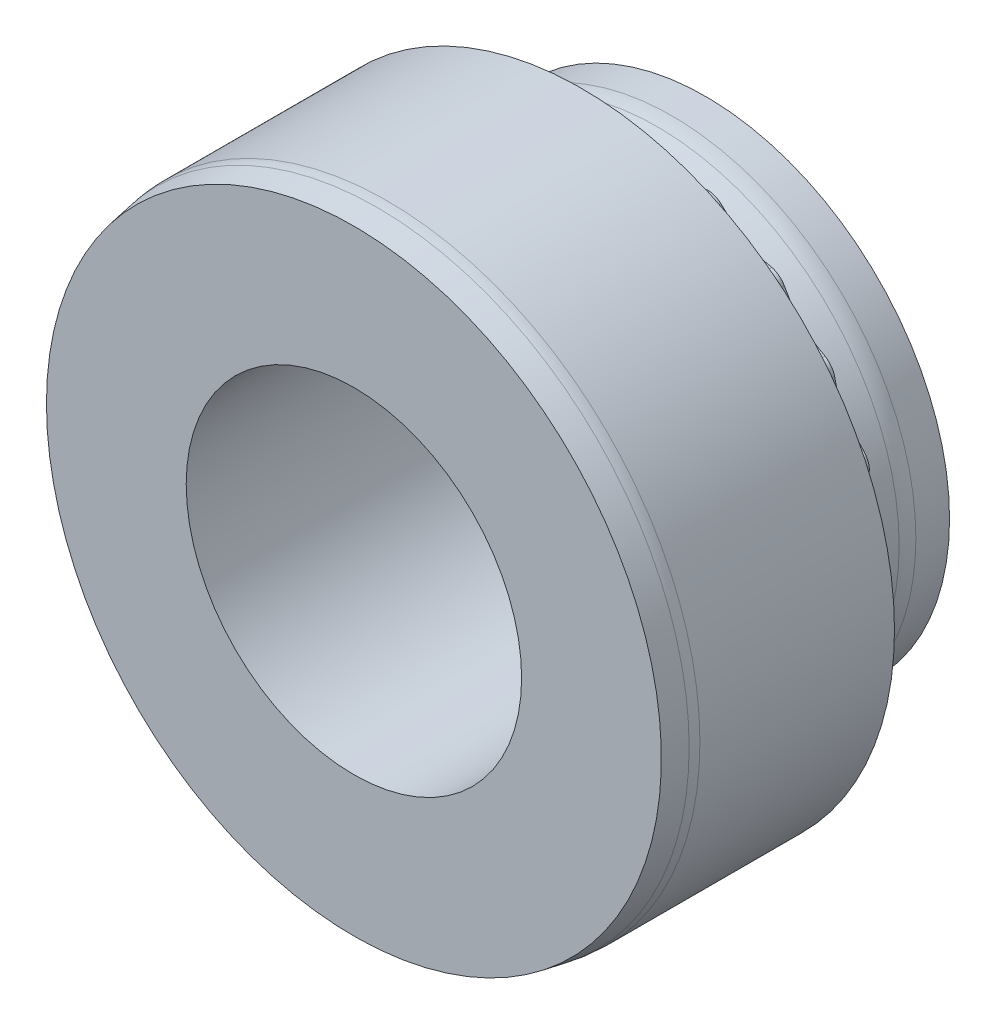
SolidWorks part; units mm, degrees
material "Alloy Steel"
ref_plane "Front Plane" through (0, 0, 0) normal (0, 0, 1) x (1, 0, 0)
ref_plane "Top Plane" through (0, 0, 0) normal (0, 1, 0) x (1, 0, 0)
ref_plane "Right Plane" through (0, 0, 0) normal (1, 0, 0) x (0, 0, -1)
sketch "Sketch1" plane through (0, 0, 0) normal (1, 0, 0) x (0, 0, -1)
  line L0 (0, -4.365) -> (0, 4.365) construction
  line L1 (0, 4.365) -> (-0.7367, 4.365) construction
  line L2 (-1.6207, 4.1281) -> (-1.6207, 5.1707) construction
  line L3 (-1.6207, 5.1707) -> (-2.21, 5.1707) construction
  line L4 (-2.21, 5.1707) -> (-2.21, 5.59) construction
  line L5 (-2.21, 5.59) -> (-6.29, 5.59) construction
  line L9 (-6.29, 0) -> (0, 0) construction
  line L10 (-6.29, -5.59) -> (-6.29, 5.59) construction
  line L11 (-0.7367, 4.365) -> (-1.6207, 4.1281) construction
  line L12 (-3.145, -3) -> (-3.145, 3) construction
  point P4 (0, 0)
  point P17 (-6.29, 0)
  point P19 (-6.29, 5.59)
  point P20 (-6.29, 0)
  point P24 (-3.145, 0)
  point P26 (-6.29, 0)
  dimension "C" = 8.73
  dimension "A" = 2.21
  dimension "Head OD" = 11.18
  dimension "D9" = 5.1707
  dimension "D10" = 0.7367
  dimension "D11" = 75
  dimension "Thread Size" = 6
  dimension "Head Height" = 4.08
  dimension "D2" = 0.5893
sketch "Sketch2" plane through (0, 0, 0) normal (1, 0, 0) x (0, 0, -1)
  line L0 (0, 0) -> (0, 4.365)
  line L1 (0, -4.365) -> (0, 4.365) construction
  line L2 (0, 4.365) -> (-0.7367, 4.365)
  line L3 (-0.7367, 4.365) -> (-1.6207, 4.1281)
  line L4 (-1.6207, 4.1281) -> (-1.6207, 5.1707)
  line L5 (-1.6207, 5.1707) -> (-2.21, 5.1707)
  line L6 (-2.21, 5.1707) -> (-2.21, 5.59)
  line L7 (-2.21, 5.59) -> (-6.29, 5.59)
  line L10 (-6.29, 0) -> (0, 0)
  line L12 (-6.29, 5.59) -> (-6.29, 0)
revolve "Revolve1" add sketch "Sketch2" angle 360 about L9
sketch "Sketch5" plane through (0, 0, 1.6207) normal (0, 0, -1) x (-1, 0, 0)
  line L0 (0, 0) -> (-5.1707, 0) construction
  line L1 (-5.1191, -0.7289) -> (-4.6537, 0)
  line L2 (-4.6537, 0) -> (-5.1191, 0.7289)
  circle A0 centre (0, 0) radius 5.1707 construction
  arc A1 (-5.1191, 0.7289) -> (-5.1191, -0.7289) centre (0, 0) ccw
  point P6 (-5.1707, 0)
  dimension "D2" = 4.6537
  dimension "D1" = 1.4627
extrude "Cut-Extrude2" cut sketch "Sketch5" against normal up to surface (0.5893 mm away) up to face at (5.59, 0, 2.21)
fillet "Fillet3" radius 0.2194 1 edges at (4.6537, 0, 1.9153)
pattern_circular "CirPattern1" count 24 over 360 about axis through (0, 0, 6.29) along (0, 0, 1) of "Cut-Extrude2", "Fillet3"
fillet "Fillet4" radius 0.2194 24 edges at (4.0656, 3.1197, 1.9153) (3.1197, 4.0656, 1.9153) (1.9611, 4.7345, 1.9153) (0.6689, 5.0808, 1.9153) (-1.9611, 4.7345, 1.9153) (-0.6689, 5.0808, 1.9153) (-3.1197, 4.0656, 1.9153) (-4.0656, 3.1197, 1.9153) (-4.7345, 1.9611, 1.9153) (-5.0808, 0.6689, 1.9153) (-4.7345, -1.9611, 1.9153) (-5.0808, -0.6689, 1.9153) (-4.0656, -3.1197, 1.9153) (-3.1197, -4.0656, 1.9153) (-1.9611, -4.7345, 1.9153) (-0.6689, -5.0808, 1.9153) (0.6689, -5.0808, 1.9153) (1.9611, -4.7345, 1.9153) (3.1197, -4.0656, 1.9153) (4.0656, -3.1197, 1.9153) (4.7345, -1.9611, 1.9153) (5.0808, -0.6689, 1.9153) (4.7345, 1.9611, 1.9153) (5.0808, 0.6689, 1.9153)
sketch "Sketch11" plane through (0, 0, 0) normal (0, 1, 0) x (1, 0, 0)
  line L0 (4.6537, -1.6207) -> (5.1707, -1.8089)
  line L2 (5.1707, -1.8089) -> (5.1707, -1.6207)
  line L3 (0, -1.6207) -> (5.1707, -1.6207) construction
  line L4 (4.6537, -1.6207) -> (5.1707, -1.6207)
  line L5 (0, -6.29) -> (0, 0) construction
  dimension "D2" = 4.6537
  dimension "D1" = 20
revolve "Cut-Revolve3" cut sketch "Sketch11" angle 360 about L9
sketch "Sketch12" plane through (0, 0, 0) normal (1, 0, 0) x (0, 0, -1)
  line L0 (-6.29, 0) -> (0, 0)
  line L1 (0, 0) -> (0, -3)
  line L2 (0, -4.365) -> (0, 4.365) construction
  line L3 (0, -3) -> (-6.29, -3)
  line L5 (-6.29, -3) -> (-6.29, 0)
revolve "Cut-Revolve4" cut sketch "Sketch12" angle 360 about L9
chamfer "Chamfer1" distance 0.51 angle 10 1 edges at (5.59, 0, 6.29) first distance on face at (5.59, 0, 6.29)
fillet "Fillet5" radius 1.02 2 edges at (-5.59, 0, 5.78) (4.365, 0, 0.7367)
sketch "Sketch17" plane through (0, 0, 6.29) normal (0, 0, 1) x (1, 0, 0)
  line L0 (0, 3) -> (0, -3) construction
  line L1 (0, 0) -> (-2.1213, -2.1213) construction
  circle A0 centre (0, 0) radius 3 construction
  point P8 (-2.1213, -2.1213)
  dimension "D1" = 45
sketch "Sketch13" [suppressed] plane through (0, 0, 0) normal (0, 0, -1) x (-1, 0, 0)
  circle A0 centre (0, 0) radius 3 construction
  circle A1 centre (0, 0) radius 3
curve "Helix/Spiral1" [suppressed] pitch 0.7937 height 7.0838 turns 8.9244 parameters "Thread Pitch"=0.7937
sketch "Sketch14" [suppressed] plane through (0, 0, 0) normal (1, 0, 0) x (0, 0, -1)
  line L0 (-0.0496, 3.0859) -> (0.7441, 3.0859) construction
  line L1 (-0.0496, 3.0859) -> (0.3473, 2.3985) construction
  line L2 (0.3473, 2.3985) -> (0.7441, 3.0859) construction
  line L3 (0.3473, 3.0859) -> (0.3473, 3) construction
  line L4 (0.3473, 2.3985) -> (0.3473, 2.4844) construction
  line L5 (0.2977, 2.4844) -> (0.3969, 2.4844) construction
  line L6 (0, 3) -> (0.6945, 3) construction
  line L7 (-0.0248, 3.043) -> (0.7193, 3.043) construction
  line L8 (-0.0248, 3.043) -> (0.7193, 3.043)
  line L9 (0.7193, 3.043) -> (0.3969, 2.4844)
  line L10 (0.3969, 2.4844) -> (0.2977, 2.4844)
  line L11 (0.2977, 2.4844) -> (-0.0248, 3.043)
  point P12 (0.3473, 3.043)
  dimension "D1" = 0.7937
  dimension "D2" = 0.0992
sweep "Sweep1" [suppressed] add profiles "Sketch14" path "Helix/Spiral1"
sketch "Sketch15" [suppressed] plane through (0, 0, 0) normal (0, 0, -1) x (-1, 0, 0)
  circle A2 centre (0, 0) radius 3.1191
  circle A3 centre (0, 0) radius 3.1191
  dimension "D1" = 0.1191
extrude "Cut-Extrude3" [suppressed] cut sketch "Sketch15" against normal through all draft 47 and the other way through all draft 47
sketch "Sketch16" [suppressed] plane through (0, 0, 6.29) normal (0, 0, 1) x (1, 0, 0)
  circle A1 centre (0, 0) radius 3.1191
  circle A2 centre (0, 0) radius 3.1191
  dimension "D1" = 0
extrude "Cut-Extrude4" [suppressed] cut sketch "Sketch16" against normal through all draft 47 and the other way through all draft 47
equation "\"D9@Sketch1\"=\"Head OD@Sketch1\" / 2 * .925"
equation "\"D10@Sketch1\"=\"A@Sketch1\" / 3"
equation "\"D1@Sketch5\" =  ( \"Head OD@Sketch1\" * 3.14 )  / 24"
equation "\"D2@Sketch5\"=\"D9@Sketch1\"*.9"
equation "\"D1@Fillet3\"=\"D1@Sketch5\"*.15"
equation "\"D1@Fillet4\"=\"D1@Fillet3\""
equation "\"D2@Sketch1\"=\"A@Sketch1\"/3.75"
equation "\"D1@Chamfer1\"=\"Head Height@Sketch1\"/8"
equation "\"D1@Fillet5\"=\"D1@Chamfer1\"*2"
equation "\"D2@Sketch11\"=\"D9@Sketch1\"*.9"
equation "\"D3@Helix/Spiral1\" = \"Thread Pitch@Helix/Spiral1\" + \"Head Height@Sketch1\" + \"A@Sketch1\""
equation "\"D2@Sketch14\"=\"D1@Sketch14\"/8"
equation "\"D1@Sketch14\" = \"Thread Pitch@Helix/Spiral1\""
equation "\"D1@Sketch15\"=\"Thread Pitch@Helix/Spiral1\"*.15"
